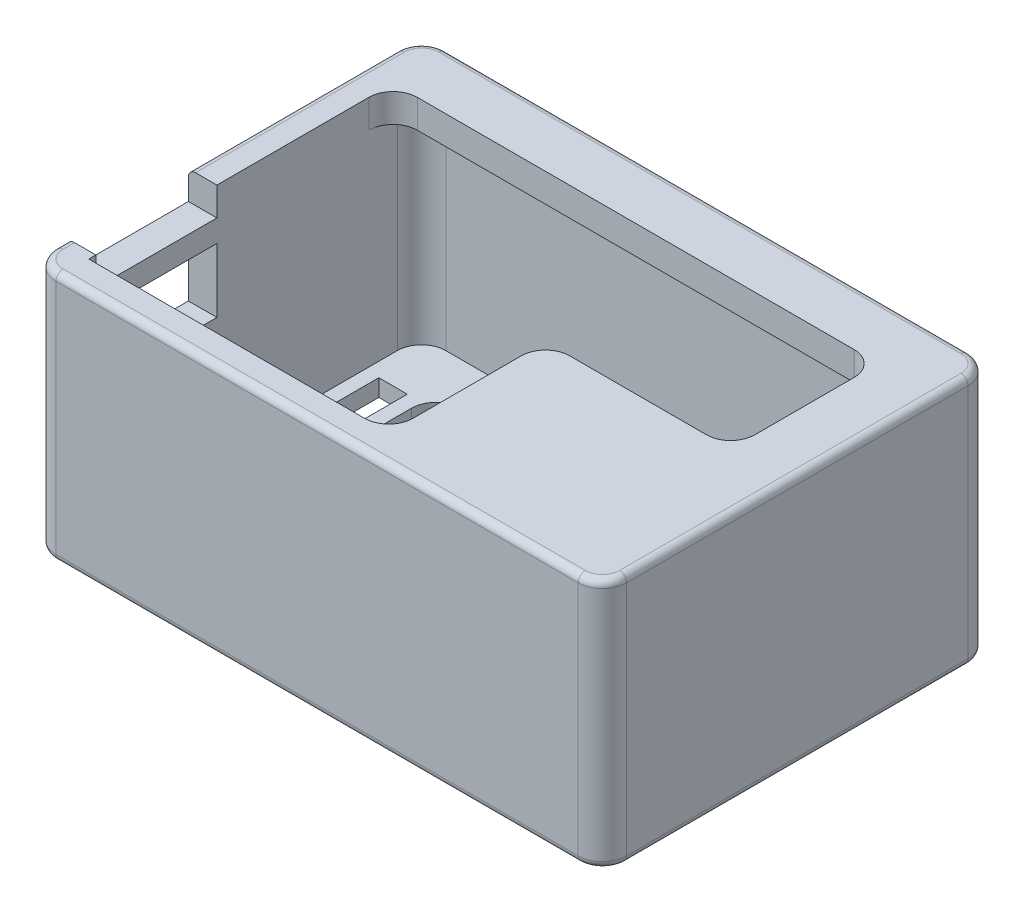
SolidWorks part; units mm, degrees
ref_plane "Front Plane" through (0, 0, 0) normal (0, 0, 1) x (1, 0, 0)
ref_plane "Top Plane" through (0, 0, 0) normal (0, 1, 0) x (1, 0, 0)
ref_plane "Right Plane" through (0, 0, 0) normal (1, 0, 0) x (0, 0, -1)
sketch "Sketch1" plane through (0, 0, 0) normal (0, 1, 0) x (1, 0, 0)
  line L1 (18.034, -11.684) -> (-18.034, -11.684)
  line L2 (18.034, -11.684) -> (18.034, 11.684)
  line L3 (18.034, 11.684) -> (-18.034, 11.684)
  line L4 (-18.034, -11.684) -> (-18.034, 11.684)
  line L5 (0, 11.684) -> (0, -11.684) construction
  line L6 (18.034, 0) -> (-18.034, 0) construction
  line L7 (20.034, -13.684) -> (-20.034, -13.684)
  line L8 (20.034, -13.684) -> (20.034, 13.684)
  line L9 (20.034, 13.684) -> (-20.034, 13.684)
  line L10 (-20.034, -13.684) -> (-20.034, 13.684)
  line L11 (0, 13.684) -> (0, -13.684)
  line L12 (20.034, 0) -> (-20.034, 0)
  point P0 (0, 0)
  point P4 (0, 0)
  dimension "D1" = 36.068
  dimension "D2" = 23.368
  dimension "D3" = 2
  dimension "D4" = 2
extrude "Boss-Extrude2" add sketch "Sketch1" along normal blind 14.4 contours L12 L4 L3 L11 L9 L10 | L12 L8 L9 L11 L3 L2 | L8 L12 L2 L1 L11 L7 | L4 L12 L10 L7 L11 L1 region at (18.2766, 0, 5.842) region at (-0.2426, 0, 12.684) region at (18.2766, 0, -5.842) region at (-19.034, 0, -0.2426)
sketch "Sketch3" plane through (0, 0, 0) normal (0, -1, 0) x (1, 0, 0)
  line L0 (18.034, 11.684) -> (-18.034, 11.684) construction
  line L1 (-20.034, 13.684) -> (20.034, 13.684)
  line L2 (-20.034, 13.684) -> (-20.034, -13.684)
  line L3 (-20.034, -13.684) -> (20.034, -13.684)
  line L4 (20.034, 13.684) -> (20.034, -13.684)
  line L5 (14.034, -8.684) -> (-14.034, -8.684)
  line L6 (14.034, -8.684) -> (14.034, 8.684)
  line L7 (14.034, 8.684) -> (-14.034, 8.684)
  line L8 (-14.034, -8.684) -> (-14.034, 8.684)
  line L9 (0, 8.684) -> (0, -8.684) construction
  line L10 (14.034, 0) -> (-14.034, 0) construction
  line L11 (-18.034, 11.684) -> (-18.034, -11.684) construction
  point P4 (0, 0)
  dimension "D1" = 3
  dimension "D2" = 4
extrude "Boss-Extrude3" add sketch "Sketch3" along normal blind 1.2 contours L5 L8 L7 L6 region at (0, 0, 13.1988)
extrude "Boss-Extrude4" add sketch "Sketch1<4>" along normal blind 2 from surface contours L9 L10 L7 L8 starting at face at (0, 14.4, 0)
sketch "Sketch1<4>" plane through (0, 0, 0) normal (0, 1, 0) x (1, 0, 0) same geometry as "Sketch1"
fillet "Fillet1" radius 1.7 7 edges at (18.034, 7.2, 11.684) (-18.034, 7.2, -11.684) (18.034, 7.2, -11.684) (20.034, 7.6, 13.684) (20.034, 7.6, -13.684) (-20.034, 7.6, -13.684) (-20.034, 7.6, 13.684)
fillet "Fillet2" radius 1.7 4 edges at (14.034, -0.6, 8.684) (-14.034, -0.6, 8.684) (-14.034, -0.6, -8.684) (14.034, -0.6, -8.684)
sketch "Sketch4" plane through (-20.034, 0, 0) normal (-1, 0, 0) x (0, 0, 1)
  line L1 (11.184, 8.35) -> (2.684, 8.35)
  line L2 (11.184, 8.35) -> (11.184, 12.85)
  line L3 (11.184, 12.85) -> (2.684, 12.85)
  line L4 (2.684, 8.35) -> (2.684, 12.85)
  line L5 (6.934, 12.85) -> (6.934, 8.35) construction
  line L6 (11.184, 10.6) -> (2.684, 10.6) construction
  line L7 (11.984, -1.2) -> (11.984, 16.4) construction
  line L8 (-11.984, 16.4) -> (11.984, 16.4) construction
  point P0 (6.934, 10.6)
  dimension "D1" = 3.55
  dimension "D2" = 4.5
  dimension "D3" = 8.5
  dimension "D4" = 0.8
extrude "Cut-Extrude1" cut sketch "Sketch4" against normal up to surface (2 mm away) up to face at (-18.034, 7.2, 0.85)
sketch "Sketch5" plane through (0, 0, 0) normal (0, -1, 0) x (-1, 0, 0)
  line L0 (18.334, 13.684) -> (-18.334, 13.684) construction
  line L1 (17.034, -2.316) -> (15.034, -2.316)
  line L2 (17.034, -2.316) -> (17.034, 7.684)
  line L3 (17.034, 7.684) -> (15.034, 7.684)
  line L4 (15.034, -2.316) -> (15.034, 7.684)
  line L5 (16.034, 7.684) -> (16.034, -2.316) construction
  line L6 (17.034, 2.684) -> (15.034, 2.684) construction
  line L7 (14.034, 6.984) -> (14.034, -6.984) construction
  point P0 (16.034, 2.684)
  dimension "D1" = 10
  dimension "D2" = 2
  dimension "D3" = 6
  dimension "D4" = 1
extrude "Cut-Extrude2" cut sketch "Sketch5" along normal blind 1.2
sketch "Sketch6" plane through (0, 16.4, 0) normal (0, 1, 0) x (1, 0, 0)
  line L0 (-20.034, -11.984) -> (-20.034, 11.984) construction
  line L1 (-20.034, -13.684) -> (16.034, -13.684)
  line L2 (-20.034, -13.684) -> (-20.034, 9.684)
  line L3 (-20.034, 9.684) -> (16.034, 9.684)
  line L4 (16.034, -13.684) -> (16.034, 9.684)
  line L5 (18.334, -13.684) -> (-18.334, -13.684) construction
  line L6 (20.034, -11.984) -> (20.034, 11.984) construction
  line L7 (18.334, 13.684) -> (-18.334, 13.684) construction
  line L9 (16.034, -13.684) -> (3.034, -13.684)
  line L10 (16.034, -13.684) -> (16.034, -0.684)
  line L11 (16.034, -0.684) -> (3.034, -0.684)
  line L12 (3.034, -13.684) -> (3.034, -0.684)
  line L13 (16.034, 9.684) -> (-18.034, 9.684)
  line L14 (16.034, 9.684) -> (16.034, -11.684)
  line L15 (16.034, -11.684) -> (-18.034, -11.684)
  line L16 (-18.034, 9.684) -> (-18.034, -11.684)
  dimension "D1" = 4
  dimension "D2" = 4
  dimension "D3" = 13
  dimension "D4" = 13
  dimension "D5" = 2
  dimension "D6" = 2
extrude "Cut-Extrude3" cut sketch "Sketch6" against normal up to surface (2 mm away) contours L3 L16 L15 L12 L11 L4 region at (-3.5751, 16.4, -0.2673) up to face at (2.3837, 14.4, -1.4766)
fillet "Fillet4" radius 1.7 5 edges at (3.034, 15.4, 0.684) (16.034, 15.4, -9.684) (16.034, 15.4, 0.684) (3.034, 15.4, 11.684) (-18.034, 15.4, -9.684)
sketch "Sketch7" plane through (-20.034, 0, 0) normal (-1, 0, 0) x (0, 0, 1)
  line L0 (-11.984, 16.4) -> (11.984, 16.4) construction
  line L1 (2.684, 16.4) -> (11.184, 16.4)
  line L2 (2.684, 16.4) -> (2.684, 14.4)
  line L3 (2.684, 14.4) -> (11.184, 14.4)
  line L4 (11.184, 16.4) -> (11.184, 14.4)
  line L5 (2.684, 12.85) -> (2.684, 8.35) construction
  line L6 (11.184, 8.35) -> (11.184, 12.85) construction
  dimension "D1" = 2
extrude "Cut-Extrude4" cut sketch "Sketch7" against normal up to surface (2 mm away) up to face at (-18.034, 10.6, 6.934)
fillet "Fillet5" radius 0.5 17 edges at (-20.034, 16.4, -4.65) (-19.5361, 16.4, -13.1861) (0, 16.4, -13.684) (19.5361, 16.4, -13.1861) (-20.034, 16.4, 11.584) (-19.5361, 16.4, 13.1861) (0, 16.4, 13.684) (19.5361, 16.4, 13.1861) (20.034, 16.4, 0) (19.5361, -1.2, 13.1861) (20.034, -1.2, 0) (19.5361, -1.2, -13.1861) (0, -1.2, -13.684) (-19.5361, -1.2, -13.1861) (-20.034, -1.2, 0) (-19.5361, -1.2, 13.1861) (0, -1.2, 13.684)
